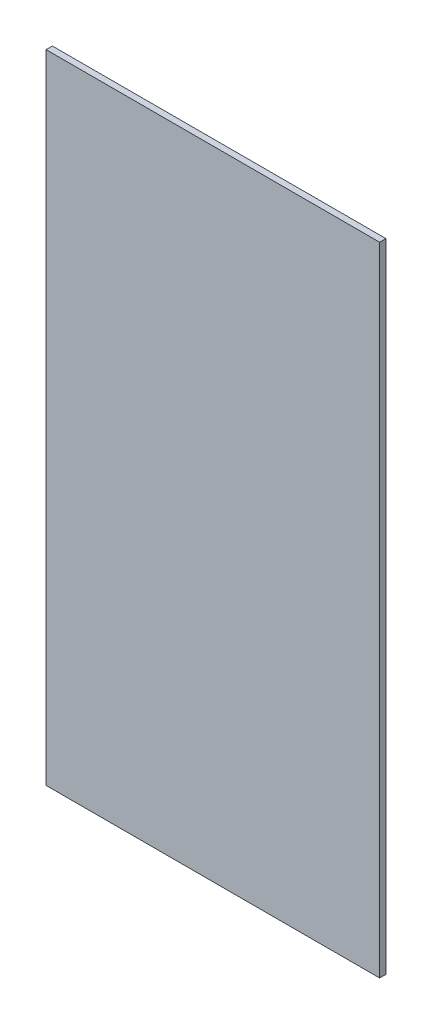
SolidWorks part; units mm, degrees
ref_plane "Спереди" through (0, 0, 0) normal (0, 0, 1) x (1, 0, 0)
ref_plane "Сверху" through (0, 0, 0) normal (0, 1, 0) x (1, 0, 0)
ref_plane "Справа" through (0, 0, 0) normal (1, 0, 0) x (0, 0, -1)
other "Configuration Table"
sketch "Эскиз1" plane through (0, 0, 0) normal (0, 0, 1) x (1, 0, 0)
  line L1 (0, -506.285) -> (-530, -506.285)
  line L2 (0, -506.285) -> (0, 506.285)
  line L3 (0, 506.285) -> (-530, 506.285)
  line L4 (-530, -506.285) -> (-530, 506.285)
extrude "Бобышка-Вытянуть1" add sketch "Эскиз1" against normal blind 10
equation "\"Ширина груза\"= 420"
equation "\"Глубина груза\"= 490"
equation "\"Высота груза\"= 297"
equation "\"Ширина ячейки\"= \"Ширина груза\" + 10"
equation "\"Глубина ячейки\"= \"Глубина груза\" + 10"
equation "\"Высота ячейки\"= \"Высота груза\" + 10 + 13"
equation "\"Колво ячеек ширина\"= 2"
equation "\"Колво ячеек высота\"= 2"
equation "\"Толщина стенки\"= 10"
equation "\"Крепление дверцы\"= 5"
equation "\"Ширина рейки\"= \"Толщина шестерни\""
equation "\"Высота рейки\"= 20"
equation "\"Высота пола\"= 20"
equation "\"Колво полозьев\"= 5"
equation "\"Отступ рейки\"= 20"
equation "\"Глубина каретки\"= \"Глубина ячейки\" + 30 + \"Мотор Y высота корпуса\" + 20"
equation "\"Длинна рейки\"= ( \"Ширина ячейки\" + \"Толщина стенки\" + \"Крепление дверцы\" ) * \"Колво ячеек ширина\" + \"Ширина ячейки выгрузки\" * \"Колво выгрузки\" + \"Толщина стенки\""
equation "\"Отступ шпильки\"= 26"
equation "\"Диаметр шпильки\"= 5"
equation "\"Длинна шпильки\"= ( \"Высота ячейки\" + \"Толщина стенки\" + \"Высота пола\" ) * \"Колво ячеек высота\" + ( \"Толщина стенки\" + \"Отступ рейки\" ) * 2 "
equation "\"Ширина пластины\"= 50  "
equation "\"Высота зона выгрузки\"= \"Высота ячейки\" * 2 + \"Толщина стенки\" * 2"
equation "\"Колво выгрузки\"= 1"
equation "\"Ширина ячейки выгрузки\"= \"Ширина ячейки\" + \"Толщина стенки\" + \"Отступ крепления мотора фиксации\"*2"
equation "\"Отступ крепления мотора фиксации\" = 30"
equation "\"Мотор X ширина корпуса\"= 42.3"
equation "\"Мотор X высота корпуса\"= 42.3"
equation "\"Мотор X длина корпуса\"= 40"
equation "\"Мотор X вылет вала\"= 19.8"
equation "\"Мотор Y ширина корпуса\"= 42.3"
equation "\"Мотор Y высота корпуса\"= 42.3"
equation "\"Мотор Y длина корпуса\"= 48"
equation "\"Мотор Y вылет вала\"= 30"
equation "\"Мотор Z ширина корпуса\"= 42"
equation "\"Мотор Z высота корпуса\"= 42"
equation "\"Мотор Z длина корпуса\"= 40"
equation "\"Мотор Z вылет вала\"= 23"
equation "\"Мотор диаметр вала ПРЕДВ\"= 5"
equation "\"Мотор шаг крепления ПРЕДВ\"= 31"
equation "\"Мотор диаметр отверстий ПРЕДВ\"= 3"
equation "\"Мотор глубина отверстий ПРЕДВ\"= 4.5"
equation "\"Мотор диаметр буртика ПРЕДВ\"= 22"
equation "\"Мотор высота буртика ПРЕДВ\"= 2"
equation "\"Мотор диаметр шкива ПРЕДВ\"= 16"
equation "\"Мотор длина шкива ПРЕДВ\"= 12"
equation "\"Мотор отступ шкива ПРЕДВ\"= 5"
equation "\"Мотор X шаг градусов\"= 1.8"
equation "\"Мотор Y шаг градусов\"= 1.8"
equation "\"Мотор Z шаг градусов\"= 1.8"
equation "\"Мотор Y диаметр ротора\"= 25.78"
equation "\"Толщина шестерни\"= 10"
equation "\"D1@Бобышка-Вытянуть1\"=\"Толщина стенки\""
